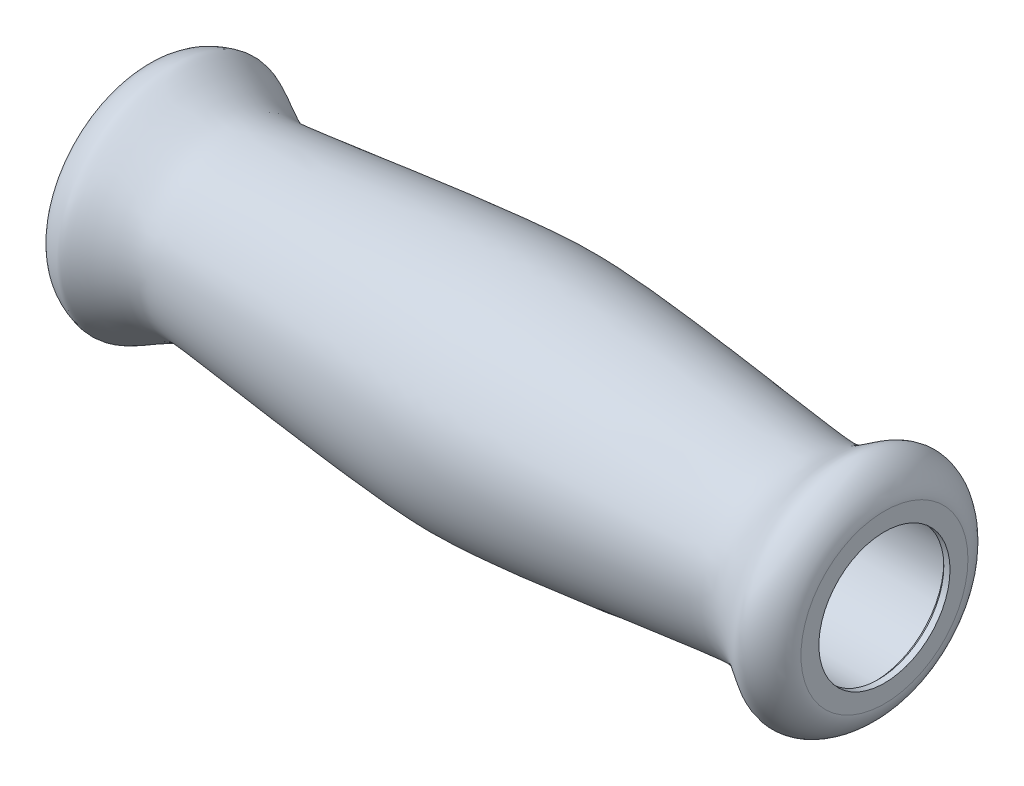
SolidWorks part; units mm, degrees
material "ABS"
ref_plane "Front Plane" through (0, 0, 0) normal (0, 0, 1) x (1, 0, 0)
ref_plane "Top Plane" through (0, 0, 0) normal (0, 1, 0) x (1, 0, 0)
ref_plane "Right Plane" through (0, 0, 0) normal (1, 0, 0) x (0, 0, -1)
sketch "Sketch1" plane through (0, 0, 0) normal (1, 0, 0) x (0, 0, -1)
  circle A0 centre (0, 0) radius 11.2
  circle A1 centre (0, 0) radius 13.5
  dimension "D1" = 22.4
  dimension "D2" = 27
extrude "Boss-Extrude1" add sketch "Sketch1" along normal blind 60
sketch "Sketch2" plane through (0, 0, 0) normal (0, 0, 1) x (1, 0, 0)
  line L0 (8, 12.6) -> (8, 9.6)
  line L1 (8, 9.6) -> (11, 9.6)
  line L2 (0, 13.5) -> (0, -13.5) construction
  arc A0 (8, 12.6) -> (11, 9.6) centre (8, 9.6) cw
  dimension "D1" = 3
  dimension "D2" = 12.6
  dimension "D3" = 8
revolve "Cut-Revolve1" cut sketch "Sketch2" angle 360 about L0
pattern_circular "CirPattern1" count 8 over 360 about axis through (60, 0, 0) along (-1, 0, 0) of "Cut-Revolve1" reverse direction yes
pattern_linear "LPattern1" count 3 spacing 20 along (1, 0, 0) of "CirPattern1"
fillet "Fillet1" radius 3 1 edges at (0, 0, -11.2)
sketch "Sketch3" plane through (0, 0, 0) normal (0, 0, 1) x (1, 0, 0)
  line L0 (0, 13.5) -> (120, 13.5)
  line L1 (5, 18.5) -> (189.4705, 18.5) construction
  line L2 (15, 14.5) -> (192.7742, 14.5) construction
  line L3 (101.9209, 18.5) -> (71.3142, 18.5) construction
  line L4 (42.1121, 14.5) -> (19.4432, 14.5) construction
  line L5 (148.8479, 14.5) -> (127.1477, 14.5) construction
  line L6 (172.1238, 18.5) -> (162.9398, 18.5) construction
  line L7 (10.2896, 18.5) -> (2.9618, 18.5) construction
  line L8 (0, 13.5) -> (0, 33.4192) construction
  line L9 (120, 13.5) -> (120, 54.919) construction
  line L10 (120, 4.0108) -> (120, 21.0324) construction
  line L11 (0, 20.3401) -> (0, 4.0345) construction
  line L12 (0, 0) -> (235.0735, 0) construction
  spline S0 degree 3 poles (0, 13.5) (0, 17.1) (3.4785, 18.244) (6.0068, 18.733) (12.1785, 14.4729) (17.5414, 14.4579) (51.1827, 18.6927) (72.2019, 18.3338) (98.0222, 14.8613) (109.1928, 14.1981) (113.0866, 18.6336) (117.428, 18.4057) (120, 15.3) (120, 13.5) knots 0 0 0 0 0.179684 0.215735 0.344425 0.376368 0.503216 0.539331 0.7014 0.734846 0.840347 0.868182 1 1 1 1
  point P23 (60, 13.5)
  dimension "D5" = 80
  dimension "D9" = 12
  dimension "D10" = 10
  dimension "D11" = 26
  dimension "D12" = 38
  dimension "D13" = 14
  dimension "D14" = 6
  dimension "D1" = 5
  dimension "D2" = 5
  dimension "D3" = 10
  dimension "D4" = 10
  dimension "D6" = 4
  dimension "D7" = 1
  dimension "D8" = 120
revolve "Revolve1" add sketch "Sketch3" angle 360 about L12
sketch "Sketch4" plane through (60, 0, 0) normal (1, 0, 0) x (0, 0, -1)
  circle A0 centre (0, 0) radius 13.5
  circle A1 centre (0, 0) radius 11.2
  circle A2 centre (0, 0) radius 13.5 construction
  circle A3 centre (0, 0) radius 11.2 construction
extrude "Boss-Extrude2" add sketch "Sketch4" along normal through all
sketch "Sketch5" plane through (120, 0, 0) normal (1, 0, 0) x (0, 0, -1)
  circle A0 centre (0, 0) radius 11.2 construction
  circle A1 centre (0, 0) radius 11.2
  circle A2 centre (0, 0) radius 10.6
  dimension "D1" = 0.6
extrude "Boss-Extrude3" add sketch "Sketch5" against normal blind 1
chamfer "Chamfer1" distance 0.6 angle 45 1 edges at (119, 0, -11.2)
